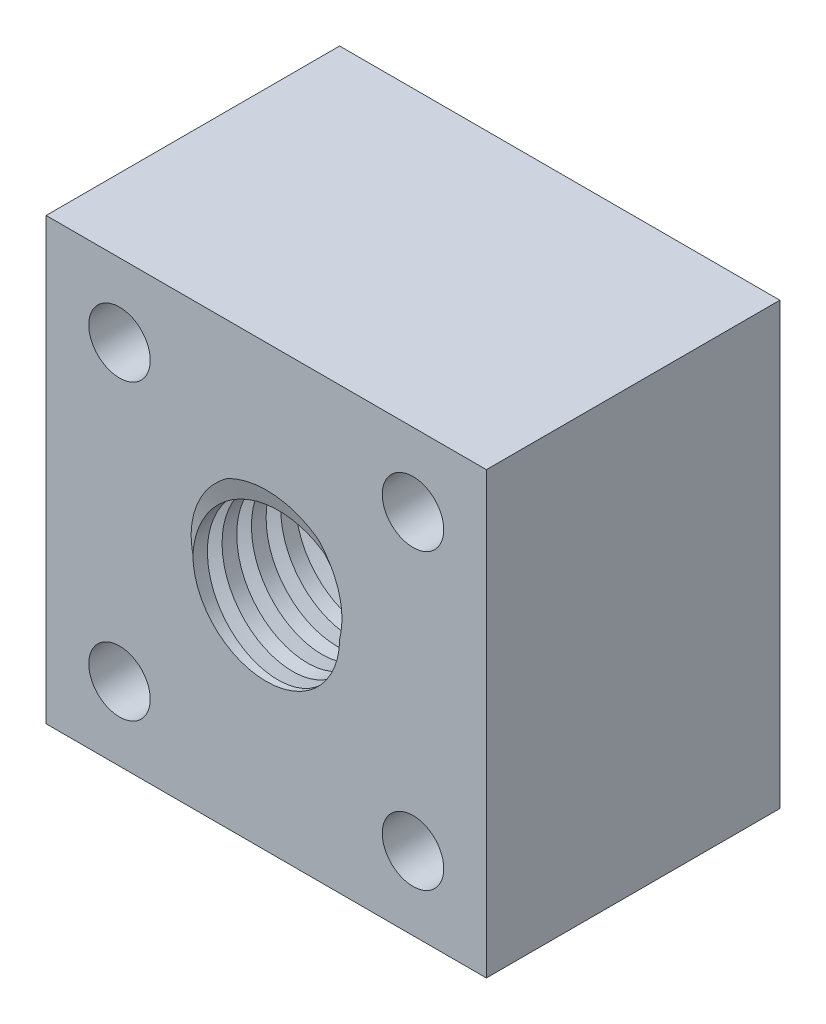
SolidWorks part; units mm, degrees
material "3003-O"
ref_plane "Front Plane" through (0, 0, 0) normal (0, 0, 1) x (1, 0, 0)
ref_plane "Top Plane" through (0, 0, 0) normal (0, 1, 0) x (1, 0, 0)
ref_plane "Right Plane" through (0, 0, 0) normal (1, 0, 0) x (0, 0, -1)
sketch "Sketch1" plane through (0, 0, 0) normal (0, 0, 1) x (1, 0, 0)
  line L1 (-15, -15) -> (15, -15)
  line L2 (-15, -15) -> (-15, 15)
  line L3 (-15, 15) -> (15, 15)
  line L4 (15, -15) -> (15, 15)
  line L5 (-15, -15) -> (15, 15) construction
  line L6 (-15, 15) -> (15, -15) construction
  circle A0 centre (-10, 10) radius 2.0942
  circle A1 centre (10, 10) radius 2.0942
  circle A2 centre (10, -10) radius 2.0942
  circle A3 centre (-10, -10) radius 2.0942
  circle A4 centre (0, 0) radius 5
  point P0 (0, 0)
  dimension "D1" = 10
  dimension "D2" = 10
  dimension "D4" = 10
  dimension "D3" = 30
extrude "Boss-Extrude1" add sketch "Sketch1" along normal blind 20
sketch "Sketch4" plane through (0, 0, 0) normal (1, 0, 0) x (0, 0, -1)
  line L0 (-20.5, 5) -> (-19.5, 5)
  line L1 (-20.5, 5) -> (-20.193, 6.25)
  line L2 (-19.5, 5) -> (-19.8632, 6.25)
  arc A0 (-20.193, 6.25) -> (-19.8632, 6.25) centre (-20.0281, 5.9994) cw
  dimension "D1" = 1.25
  dimension "D2" = 1.25
  dimension "D3" = 1
  dimension "D4" = 30
  dimension "D5" = 76.2
sketch "Sketch5" plane through (0, 0, 20) normal (0, 0, 1) x (1, 0, 0)
  circle A0 centre (0, 0) radius 5
curve "Helix/Spiral1" pitch 2 height 21.5 turns 10.75
sweep "Cut-Sweep1" cut profiles "Sketch4" path "Helix/Spiral1"
